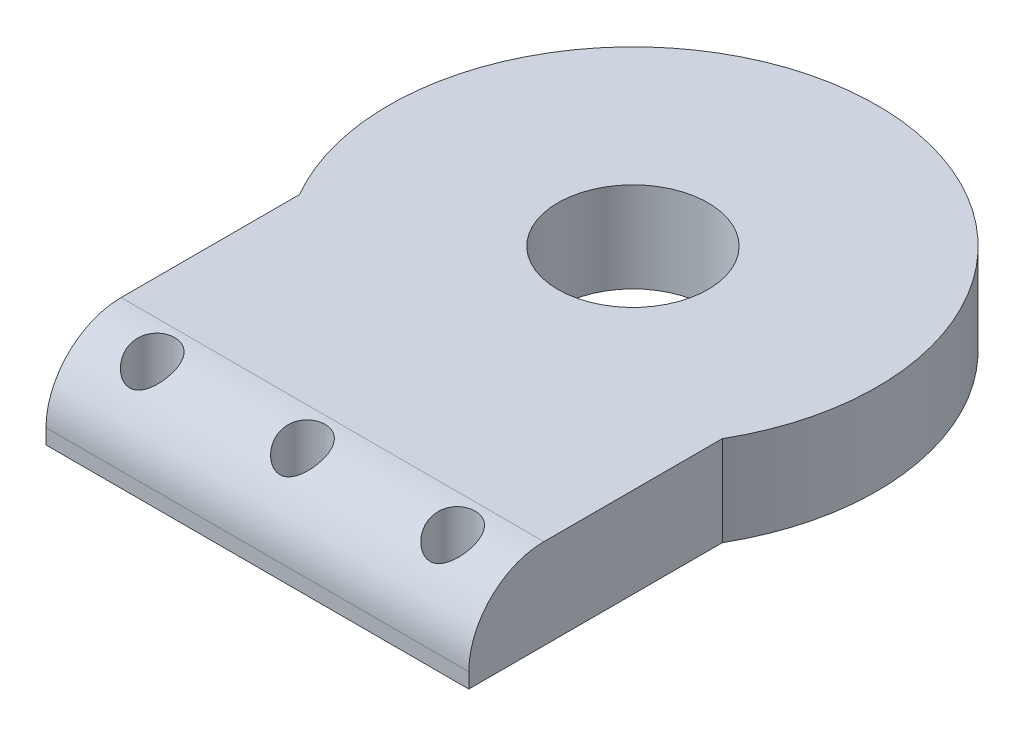
SolidWorks part; units mm, degrees
ref_plane "前视基准面" through (0, 0, 0) normal (0, 0, 1) x (1, 0, 0)
ref_plane "上视基准面" through (0, 0, 0) normal (0, 1, 0) x (1, 0, 0)
ref_plane "右视基准面" through (0, 0, 0) normal (1, 0, 0) x (0, 0, -1)
sketch "草图1" plane through (0, 0, 0) normal (0, 1, 0) x (1, 0, 0)
  line L0 (0, 0) -> (0, 50)
  line L1 (0, 50) -> (28.1458, 33.75)
  line L2 (0, 50) -> (-28.1458, 33.75)
  line L3 (0, 0) -> (-28.1458, 0)
  line L4 (-28.1458, 0) -> (-28.1458, 33.75)
  line L5 (0, 0) -> (28.1458, 0)
  line L6 (28.1458, 0) -> (28.1458, 33.75)
  circle A0 centre (0, 50) radius 32.5
extrude "凸台-拉伸1" add sketch "草图1" along normal blind 12 contours L1 A0 L2 | L0 A0 L1 | L2 A0 L0 | A0 L4 L3 L0 | A0 L0 L5 L6 region at (-15.6538, 0, -11.5799) region at (15.6538, 0, -11.5799) region at (-10.3451, 0, -32.0818) region at (10.3451, 0, -32.0818) region at (0, 0, -58.9591)
sketch "草图2" plane through (0, 0, 0) normal (0, -1, 0) x (-1, 0, 0)
  line L0 (0, 0) -> (0, 12)
  line L1 (0, 12) -> (28.1458, 12)
  line L2 (28.1458, 0) -> (28.1458, 33.75) construction
  line L3 (28.1458, 12) -> (0, 12)
  line L4 (0, 12) -> (-28.1458, 12)
  line L5 (-28.1458, 0) -> (-28.1458, 33.75) construction
  line L6 (0, 6) -> (20, 6)
  line L7 (0, 6) -> (-20, 6)
  circle A0 centre (0, 6) radius 3
  circle A1 centre (20, 6) radius 3
  circle A2 centre (-20, 6) radius 3
extrude "切除-拉伸1" cut sketch "草图2" against normal blind 12 contours A2 | L0 A0 L6 | L7 A0 L0 | L0 A0 L7 | L6 A0 L0 | A1 region at (1.2732, 0, -4.7268) region at (22.9151, 0, -6) region at (-20, 0, -8.9151) region at (-1.2732, 0, -4.7268) region at (1.2732, 0, -7.2732) region at (-1.2732, 0, -7.2732)
fillet "圆角1" radius 10 1 edges at (0, 12, 0)
sketch "草图3" plane through (0, 12, 0) normal (0, 1, 0) x (1, 0, 0)
  circle A0 centre (0, 50) radius 10
extrude "切除-拉伸2" cut sketch "草图3" against normal blind 12
